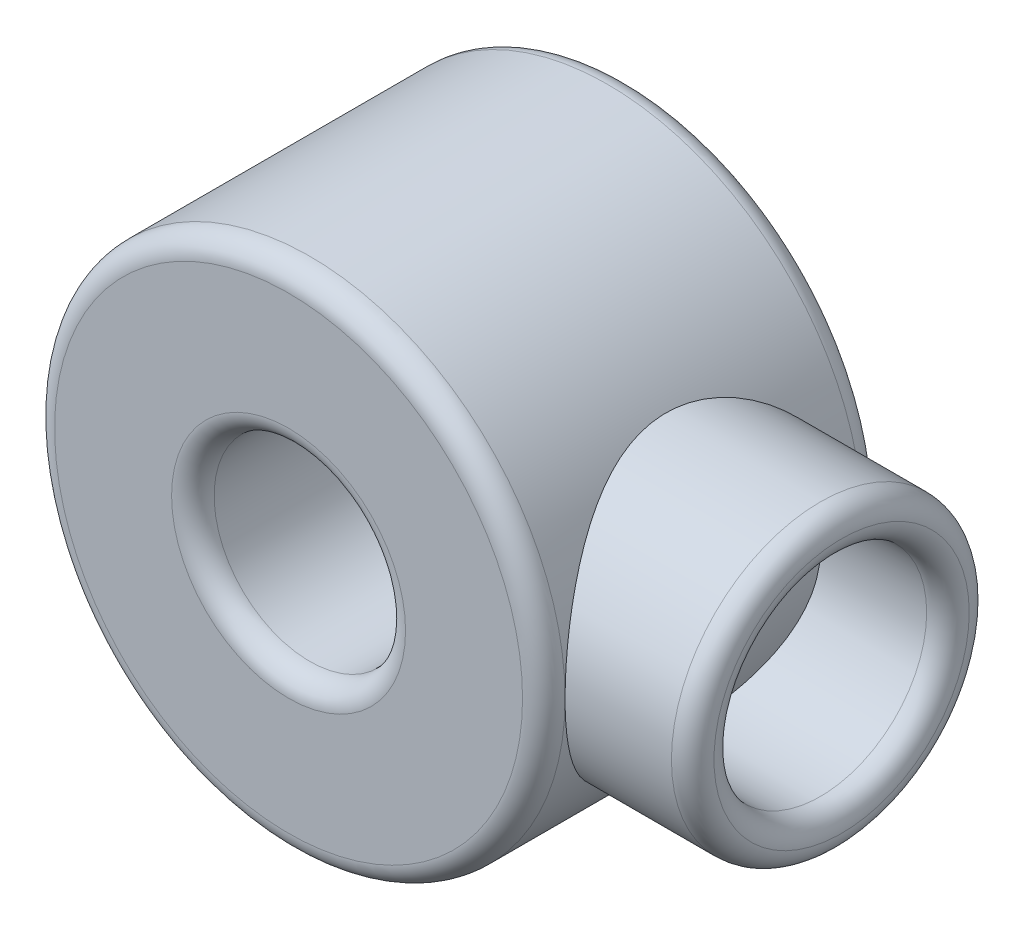
SolidWorks part; units mm, degrees
ref_plane "Front" through (0, 0, 0) normal (0, 0, 1) x (1, 0, 0)
ref_plane "Top" through (0, 0, 0) normal (0, 1, 0) x (1, 0, 0)
ref_plane "Right" through (0, 0, 0) normal (1, 0, 0) x (0, 0, -1)
sketch "Sketch1" plane through (0, 0, 0) normal (0, 0, 1) x (1, 0, 0)
  circle A0 centre (0, 0) radius 14.2875
  circle A1 centre (0, 0) radius 38.1
  dimension "D1" = 28.575
  dimension "D2" = 76.2
extrude "Boss-Extrude1" add sketch "Sketch1" along normal mid plane 50.8
ref_plane "Plane1" through (31.75, 0, 0) normal (1, 0, 0) x (0, 0, -1)
sketch "Sketch2" plane through (31.75, 0, 0) normal (1, 0, 0) x (0, 0, -1)
  circle A0 centre (0, 0) radius 15.875
  circle A1 centre (0, 0) radius 22.225
  dimension "D1" = 31.75
  dimension "D2" = 6.35
extrude "Boss-Extrude2" add sketch "Sketch2" along normal blind 25.4 and the other way blind 2.54
fillet "Fillet1" radius 3.175 6 edges at (14.2875, 0, -25.4) (38.1, 0, -25.4) (57.15, 0, -15.875) (57.15, 0, -22.225) (14.2875, 0, 25.4) (38.1, 0, 25.4)
